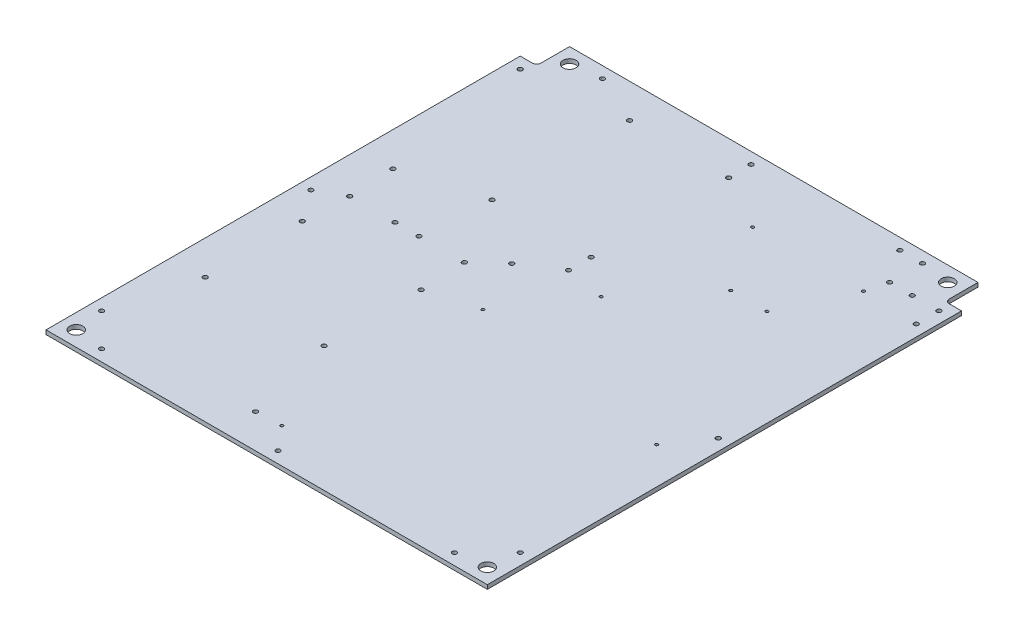
SolidWorks part; units mm, degrees
ref_plane "Front" through (0, 0, 0) normal (0, 0, 1) x (1, 0, 0)
ref_plane "Top" through (0, 0, 0) normal (0, 1, 0) x (1, 0, 0)
ref_plane "Right" through (0, 0, 0) normal (1, 0, 0) x (0, 0, -1)
sketch "Sketch1" plane through (0, 0, 0) normal (0, 1, 0) x (1, 0, 0)
  line L1 (170.434, -195.834) -> (-170.434, -195.834)
  line L2 (170.434, -195.834) -> (170.434, 195.834)
  line L3 (170.434, 195.834) -> (-170.434, 195.834)
  line L4 (-170.434, -195.834) -> (-170.434, 195.834)
  line L5 (170.434, -195.834) -> (-170.434, 195.834) construction
  line L6 (170.434, 195.834) -> (-170.434, -195.834) construction
  point P0 (0, 0)
  dimension "D1" = 340.868
  dimension "D2" = 391.668
extrude "Boss-Extrude1" add sketch "Sketch1" along normal blind 3.175
sketch "Sketch2" plane through (0, 3.175, 0) normal (0, 1, 0) x (1, 0, 0)
  line L0 (170.434, 195.834) -> (-170.434, 195.834) construction
  line L1 (-170.434, 195.834) -> (-157.734, 195.834)
  line L2 (-170.434, 195.834) -> (-170.434, 170.434)
  line L3 (-170.434, 170.434) -> (-160.909, 170.434)
  line L4 (-157.734, 195.834) -> (-157.734, 173.609)
  line L5 (170.434, 195.834) -> (157.734, 195.834)
  line L6 (170.434, 195.834) -> (170.434, 170.434)
  line L7 (170.434, 170.434) -> (160.909, 170.434)
  line L8 (157.734, 195.834) -> (157.734, 173.609)
  arc A0 (-157.734, 173.609) -> (-160.909, 170.434) centre (-160.909, 173.609) cw
  arc A1 (157.734, 173.609) -> (160.909, 170.434) centre (160.909, 173.609) ccw
  dimension "D1" = 3.175
  dimension "D2" = 25.4
  dimension "D3" = 12.7
extrude "Cut-Extrude1" cut sketch "Sketch2" against normal blind 10
hole_wizard "3/8 Clearance Hole1" positions "Sketch3" profile "Sketch4" hole size "3/8" standard "ANSI Inch" end condition through all
sketch "Sketch3" plane through (0, 3.175, 0) normal (0, 1, 0) x (1, 0, 0)
  line L0 (158.75, -184.15) -> (0, -184.15) construction
  line L1 (0, -184.15) -> (-158.75, -184.15) construction
  line L2 (-158.75, -184.15) -> (-158.75, -12.7) construction
  line L3 (-158.75, -12.7) -> (-158.75, 158.75) construction
  line L4 (-158.75, 158.75) -> (158.75, 158.75) construction
  line L5 (158.75, 158.75) -> (158.75, -12.7) construction
  line L6 (158.75, -12.7) -> (158.75, -184.15) construction
  line L8 (146.05, 184.15) -> (0, 184.15) construction
  line L9 (0, 184.15) -> (-146.05, 184.15) construction
  line L10 (-146.05, 184.15) -> (-157.734, 195.834) construction
  line L12 (157.734, 195.834) -> (146.05, 184.15) construction
  line L14 (-158.75, 158.75) -> (-170.434, 170.434) construction
  line L16 (-158.75, -184.15) -> (-170.434, -195.834) construction
  line L18 (158.75, 158.75) -> (170.434, 170.434) construction
  line L20 (158.75, -184.15) -> (170.434, -195.834) construction
  line L21 (158.75, -184.15) -> (158.75, -195.834) construction
  line L22 (-170.434, -195.834) -> (170.434, -195.834) construction
  line L24 (158.75, -184.15) -> (170.434, -184.15) construction
  line L25 (170.434, -195.834) -> (170.434, 170.434) construction
  point P0 (158.75, -184.15)
  point P2 (-158.75, -184.15)
  point P94 (-146.05, 184.15)
  point P96 (146.05, 184.15)
  dimension "D1" = 11.684
sketch "Sketch4" plane through (158.75, 3.175, 184.15) normal (1, 0, 0) x (0, 0, 1)
  line L0 (0, 0) -> (0, 3.175)
  line L1 (0, 3.175) -> (5.0419, 3.175)
  line L2 (5.0419, 3.175) -> (5.0419, 0)
  line L5 (5.0419, 0) -> (0, 0)
  line L11 (0, -6.35) -> (0, 107.95) construction
  dimension "Thru Hole Dia." = 10.0838
  dimension "Thru Hole Depth" = 3.175
hole_wizard "#4-40 Tapped Hole2" positions "Sketch9" profile "Sketch10" tap size "#4-40" standard "ANSI Inch" end condition through all
sketch "Sketch9" plane through (0, 3.175, 0) normal (0, 1, 0) x (1, 0, 0)
  circle A0 centre (33.725, 145.759) radius 1.6319 construction
  circle A1 centre (119.375, 145.759) radius 1.6319 construction
  point P4 (119.375, 145.759)
  point P6 (33.725, 145.759)
  point P20 (21.73, 40.754)
  point P23 (67.7, 94.894)
  point P26 (95.6, 94.894)
  point P30 (-15.34, -13.51)
  point P33 (142.14, -36.73)
  point P36 (142.14, -36.73)
  point P39 (-15.34, -168.81)
cosmetic thread "Hole Thread17" parameters "D2"=2.8448
cosmetic thread "Hole Thread18" parameters "D2"=2.8448
sketch "Sketch10" plane through (119.375, 3.175, -145.759) normal (1, 0, 0) x (0, 0, 1)
  line L0 (0, 0) -> (0, 3.175)
  line L1 (0, 3.175) -> (1.1303, 3.175)
  line L2 (1.1303, 3.175) -> (1.1303, 0)
  line L5 (1.1303, 0) -> (0, 0)
  line L11 (0, -6.35) -> (0, 107.95) construction
  dimension "Thru Tap Drill Dia." = 2.2606
  dimension "Thru Tap Drill Depth" = 3.175
cosmetic thread "Hole Thread19" parameters "D2"=2.8448
cosmetic thread "Hole Thread20" parameters "D2"=2.8448
cosmetic thread "Hole Thread21" parameters "D2"=2.8448
cosmetic thread "Hole Thread22" parameters "D2"=2.8448
cosmetic thread "Hole Thread23" parameters "D2"=2.8448
cosmetic thread "Hole Thread24" parameters "D2"=2.8448
cosmetic thread "Hole Thread25" parameters "D2"=2.8448
hole_wizard "#8-32 Tapped Hole2" positions "Sketch13" profile "Sketch14" tap size "#8-32" standard "ANSI Inch" end condition through all
sketch "Sketch13" plane through (0, 3.175, 0) normal (0, 1, 0) x (1, 0, 0)
  line L34 (-161.684, 161.684) -> (-161.684, -161.684)
  line L36 (161.684, 144.184) -> (161.684, -161.684)
  line L38 (-123.584, 187.084) -> (106.084, 187.084)
  line L39 (106.084, 187.084) -> (123.584, 187.084)
  line L40 (123.584, 187.084) -> (123.584, 161.684)
  line L42 (123.584, 161.684) -> (141.084, 161.684)
  line L43 (141.084, 161.684) -> (161.684, 161.684)
  line L45 (161.684, 161.684) -> (161.684, 144.184)
  line L47 (-8.584, 187.084) -> (-8.584, 169.584)
  line L48 (-8.584, 169.584) -> (-8.584, 63.334)
  line L50 (-8.584, 63.334) -> (-8.584, 45.834)
  line L51 (-8.584, 45.834) -> (-144.184, 45.834)
  line L52 (-144.184, 45.834) -> (-161.684, 45.834)
  line L54 (-34.884, 45.834) -> (-34.884, 28.334)
  line L55 (-34.884, 28.334) -> (-34.884, -169.584)
  line L56 (-34.884, -169.584) -> (-34.884, -187.084)
  line L58 (-136.284, -187.084) -> (136.284, -187.084)
  line L60 (-161.684, -24.166) -> (-144.184, -24.166)
  line L61 (-144.184, -24.166) -> (-52.384, -24.166)
  line L62 (-52.384, -24.166) -> (-34.884, -24.166)
  line L64 (-161.684, -99.166) -> (-144.184, -99.166)
  line L65 (-144.184, -99.166) -> (-52.384, -99.166)
  line L66 (-52.384, -99.166) -> (-34.884, -99.166)
  line L68 (-161.684, 10.834) -> (-142.534, 10.834)
  line L69 (-142.534, 10.834) -> (-107.534, 10.834)
  line L70 (-107.534, 10.834) -> (-89.034, 10.834)
  line L71 (-89.034, 10.834) -> (-54.034, 10.834)
  line L72 (-54.034, 10.834) -> (-34.884, 10.834)
  line L74 (-85.134, 45.834) -> (-85.134, 63.334)
  line L75 (-85.134, 63.334) -> (-85.134, 169.584)
  line L76 (-85.134, 169.584) -> (-85.134, 187.084)
  line L78 (-170.434, 170.434) -> (-170.434, -195.834) construction
  line L79 (157.734, 195.834) -> (-157.734, 195.834) construction
  line L81 (170.434, -195.834) -> (170.434, 170.434) construction
  line L82 (-170.434, -195.834) -> (170.434, -195.834) construction
  line L83 (-170.434, 170.434) -> (-160.909, 170.434) construction
  line L84 (160.909, 170.434) -> (170.434, 170.434) construction
  line L85 (157.734, 195.834) -> (157.734, 173.609) construction
  line L86 (-157.734, 173.609) -> (-157.734, 195.834) construction
  line L87 (-76.384, 45.834) -> (-76.384, 10.834) construction
  line L88 (-76.384, 10.834) -> (-76.384, -24.166) construction
  line L90 (-161.684, 63.334) -> (-85.134, 63.334) construction
  line L92 (-85.134, 63.334) -> (-8.584, 63.334) construction
  point P146 (-161.684, -161.684)
  point P148 (-161.684, 0)
  point P150 (-161.684, 161.684)
  point P152 (-144.184, 45.834)
  point P154 (-8.584, 45.834)
  point P156 (-144.184, -24.166)
  point P158 (-52.384, -24.166)
  point P160 (-144.184, -99.166)
  point P162 (-52.384, -99.166)
  point P164 (-34.884, 28.334)
  point P166 (-34.884, -169.584)
  point P168 (-136.284, -187.084)
  point P170 (0, -187.084)
  point P172 (136.284, -187.084)
  point P174 (161.684, -161.684)
  point P176 (161.684, -8.75)
  point P178 (161.684, 144.184)
  point P180 (141.084, 161.684)
  point P182 (161.684, 161.684)
  point P184 (123.584, 161.684)
  point P186 (123.584, 187.084)
  point P188 (106.084, 187.084)
  point P190 (-123.584, 187.084)
  point P192 (-8.75, 187.084)
  point P194 (-8.584, 169.584)
  point P196 (-8.584, 63.334)
  point P198 (-142.534, 10.834)
  point P200 (-107.534, 10.834)
  point P202 (-89.034, 10.834)
  point P204 (-54.034, 10.834)
  point P206 (-85.134, 63.334)
  point P208 (-85.134, 169.584)
  dimension "D1" = 8.75
  dimension "D2" = 8.75
  dimension "D3" = 8.75
  dimension "D4" = 8.75
  dimension "D5" = 34.15
  dimension "D6" = 8.75
  dimension "D7" = 8.75
  dimension "D8" = 17.5
  dimension "D9" = 34.15
  dimension "D10" = 17.5
  dimension "D11" = 17.5
  dimension "D12" = 34.15
  dimension "D13" = 34.15
  dimension "D14" = 34.15
  dimension "D15" = 34.15
  dimension "D16" = 17.5
  dimension "D17" = 17.5
  dimension "D18" = 17.5
  dimension "D19" = 17.5
  dimension "D20" = 17.5
  dimension "D21" = 17.5
  dimension "D22" = 17.5
  dimension "D23" = 17.5
  dimension "D24" = 150
  dimension "D25" = 161.85
  dimension "D26" = 135.55
  dimension "D27" = 70
  dimension "D28" = 75
  dimension "D29" = 35
  dimension "D30" = 35
  dimension "D31" = 53.5
sketch "Sketch14" plane through (-161.684, 3.175, 161.684) normal (1, 0, 0) x (0, 0, 1)
  line L0 (0, 0) -> (0, 3.175)
  line L1 (0, 3.175) -> (1.7272, 3.175)
  line L2 (1.7272, 3.175) -> (1.7272, 0)
  line L5 (1.7272, 0) -> (0, 0)
  line L11 (0, -6.35) -> (0, 107.95) construction
  dimension "Thread Major Dia." = 3.4544
  dimension "Thru Tap Drill Depth" = 3.175
